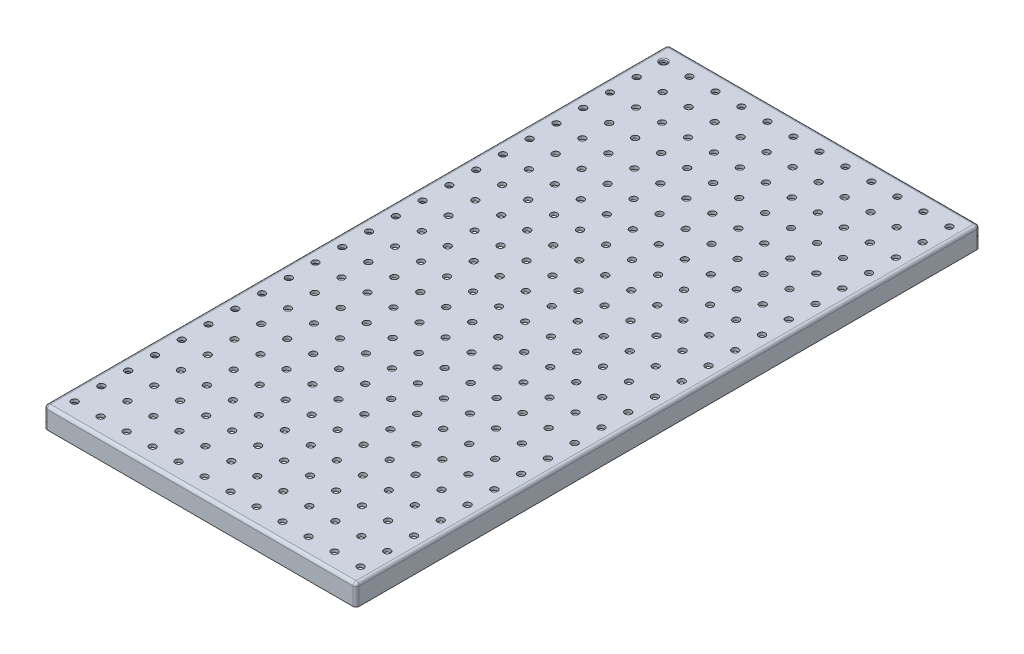
SolidWorks part; units mm, degrees
ref_plane "Alzado" through (0, 0, 0) normal (0, 0, 1) x (1, 0, 0)
ref_plane "Planta" through (0, 0, 0) normal (0, 1, 0) x (1, 0, 0)
ref_plane "Vista lateral" through (0, 0, 0) normal (1, 0, 0) x (0, 0, -1)
sketch "Croquis1" plane through (0, 0, 0) normal (0, 1, 0) x (1, 0, 0)
  line L1 (150, -300) -> (-150, -300)
  line L2 (150, -300) -> (150, 300)
  line L3 (150, 300) -> (-150, 300)
  line L4 (-150, -300) -> (-150, 300)
  line L5 (150, -300) -> (-150, 300) construction
  line L6 (150, 300) -> (-150, -300) construction
  point P0 (0, 0)
  dimension "D1" = 600
  dimension "D2" = 300
extrude "Saliente-Extruir1" add sketch "Croquis1" along normal blind 20
shell "Vaciado1" thickness 3 removed face at (0, 0, 0)
sketch "Croquis4" plane through (0, 20, 0) normal (0, 1, 0) x (1, 0, 0)
  line L0 (-137.5, 283.1945) -> (-137.5, 300) construction
  line L1 (150, 300) -> (-150, 300) construction
  line L2 (-137.5, 283.1945) -> (-150, 283.1945) construction
  line L3 (-150, 300) -> (-150, -300) construction
  line L4 (137.5, 283.1945) -> (150, 283.1945) construction
  line L5 (150, -300) -> (150, 300) construction
  line L6 (-137.5, 283.1945) -> (-112.5, 283.1945) construction
  line L7 (-137.5, 257.4495) -> (-125, 257.4495) construction
  line L8 (-125, 257.4495) -> (-125, 283.1945) construction
  line L9 (-112.5, -283.1945) -> (-112.5, -300) construction
  line L10 (-150, -300) -> (150, -300) construction
  circle A0 centre (-137.5, 283.1945) radius 3.175
  circle A1 centre (-112.5, 283.1945) radius 3.175
  circle A2 centre (-87.5, 283.1945) radius 3.175
  circle A3 centre (-62.5, 283.1945) radius 3.175
  circle A4 centre (-37.5, 283.1945) radius 3.175
  circle A5 centre (-12.5, 283.1945) radius 3.175
  circle A6 centre (12.5, 283.1945) radius 3.175
  circle A7 centre (37.5, 283.1945) radius 3.175
  circle A8 centre (62.5, 283.1945) radius 3.175
  circle A9 centre (87.5, 283.1945) radius 3.175
  circle A10 centre (112.5, 283.1945) radius 3.175
  circle A11 centre (137.5, 283.1945) radius 3.175
  circle A12 centre (-137.5, 257.4495) radius 3.175
  circle A13 centre (-112.5, 257.4495) radius 3.175
  circle A14 centre (-87.5, 257.4495) radius 3.175
  circle A15 centre (-62.5, 257.4495) radius 3.175
  circle A16 centre (-37.5, 257.4495) radius 3.175
  circle A17 centre (-12.5, 257.4495) radius 3.175
  circle A18 centre (12.5, 257.4495) radius 3.175
  circle A19 centre (37.5, 257.4495) radius 3.175
  circle A20 centre (62.5, 257.4495) radius 3.175
  circle A21 centre (87.5, 257.4495) radius 3.175
  circle A22 centre (112.5, 257.4495) radius 3.175
  circle A23 centre (137.5, 257.4495) radius 3.175
  circle A24 centre (-137.5, 231.7046) radius 3.175
  circle A25 centre (-112.5, 231.7046) radius 3.175
  circle A26 centre (-87.5, 231.7046) radius 3.175
  circle A27 centre (-62.5, 231.7046) radius 3.175
  circle A28 centre (-37.5, 231.7046) radius 3.175
  circle A29 centre (-12.5, 231.7046) radius 3.175
  circle A30 centre (12.5, 231.7046) radius 3.175
  circle A31 centre (37.5, 231.7046) radius 3.175
  circle A32 centre (62.5, 231.7046) radius 3.175
  circle A33 centre (87.5, 231.7046) radius 3.175
  circle A34 centre (112.5, 231.7046) radius 3.175
  circle A35 centre (137.5, 231.7046) radius 3.175
  circle A36 centre (-137.5, 205.9596) radius 3.175
  circle A37 centre (-112.5, 205.9596) radius 3.175
  circle A38 centre (-87.5, 205.9596) radius 3.175
  circle A39 centre (-62.5, 205.9596) radius 3.175
  circle A40 centre (-37.5, 205.9596) radius 3.175
  circle A41 centre (-12.5, 205.9596) radius 3.175
  circle A42 centre (12.5, 205.9596) radius 3.175
  circle A43 centre (37.5, 205.9596) radius 3.175
  circle A44 centre (62.5, 205.9596) radius 3.175
  circle A45 centre (87.5, 205.9596) radius 3.175
  circle A46 centre (112.5, 205.9596) radius 3.175
  circle A47 centre (137.5, 205.9596) radius 3.175
  circle A48 centre (-137.5, 180.2147) radius 3.175
  circle A49 centre (-112.5, 180.2147) radius 3.175
  circle A50 centre (-87.5, 180.2147) radius 3.175
  circle A51 centre (-62.5, 180.2147) radius 3.175
  circle A52 centre (-37.5, 180.2147) radius 3.175
  circle A53 centre (-12.5, 180.2147) radius 3.175
  circle A54 centre (12.5, 180.2147) radius 3.175
  circle A55 centre (37.5, 180.2147) radius 3.175
  circle A56 centre (62.5, 180.2147) radius 3.175
  circle A57 centre (87.5, 180.2147) radius 3.175
  circle A58 centre (112.5, 180.2147) radius 3.175
  circle A59 centre (137.5, 180.2147) radius 3.175
  circle A60 centre (-137.5, 154.4697) radius 3.175
  circle A61 centre (-112.5, 154.4697) radius 3.175
  circle A62 centre (-87.5, 154.4697) radius 3.175
  circle A63 centre (-62.5, 154.4697) radius 3.175
  circle A64 centre (-37.5, 154.4697) radius 3.175
  circle A65 centre (-12.5, 154.4697) radius 3.175
  circle A66 centre (12.5, 154.4697) radius 3.175
  circle A67 centre (37.5, 154.4697) radius 3.175
  circle A68 centre (62.5, 154.4697) radius 3.175
  circle A69 centre (87.5, 154.4697) radius 3.175
  circle A70 centre (112.5, 154.4697) radius 3.175
  circle A71 centre (137.5, 154.4697) radius 3.175
  circle A72 centre (-137.5, 128.7248) radius 3.175
  circle A73 centre (-112.5, 128.7248) radius 3.175
  circle A74 centre (-87.5, 128.7248) radius 3.175
  circle A75 centre (-62.5, 128.7248) radius 3.175
  circle A76 centre (-37.5, 128.7248) radius 3.175
  circle A77 centre (-12.5, 128.7248) radius 3.175
  circle A78 centre (12.5, 128.7248) radius 3.175
  circle A79 centre (37.5, 128.7248) radius 3.175
  circle A80 centre (62.5, 128.7248) radius 3.175
  circle A81 centre (87.5, 128.7248) radius 3.175
  circle A82 centre (112.5, 128.7248) radius 3.175
  circle A83 centre (137.5, 128.7248) radius 3.175
  circle A84 centre (-137.5, 102.9798) radius 3.175
  circle A85 centre (-112.5, 102.9798) radius 3.175
  circle A86 centre (-87.5, 102.9798) radius 3.175
  circle A87 centre (-62.5, 102.9798) radius 3.175
  circle A88 centre (-37.5, 102.9798) radius 3.175
  circle A89 centre (-12.5, 102.9798) radius 3.175
  circle A90 centre (12.5, 102.9798) radius 3.175
  circle A91 centre (37.5, 102.9798) radius 3.175
  circle A92 centre (62.5, 102.9798) radius 3.175
  circle A93 centre (87.5, 102.9798) radius 3.175
  circle A94 centre (112.5, 102.9798) radius 3.175
  circle A95 centre (137.5, 102.9798) radius 3.175
  circle A96 centre (-137.5, 77.2349) radius 3.175
  circle A97 centre (-112.5, 77.2349) radius 3.175
  circle A98 centre (-87.5, 77.2349) radius 3.175
  circle A99 centre (-62.5, 77.2349) radius 3.175
  circle A100 centre (-37.5, 77.2349) radius 3.175
  circle A101 centre (-12.5, 77.2349) radius 3.175
  circle A102 centre (12.5, 77.2349) radius 3.175
  circle A103 centre (37.5, 77.2349) radius 3.175
  circle A104 centre (62.5, 77.2349) radius 3.175
  circle A105 centre (87.5, 77.2349) radius 3.175
  circle A106 centre (112.5, 77.2349) radius 3.175
  circle A107 centre (137.5, 77.2349) radius 3.175
  circle A108 centre (-137.5, 51.4899) radius 3.175
  circle A109 centre (-112.5, 51.4899) radius 3.175
  circle A110 centre (-87.5, 51.4899) radius 3.175
  circle A111 centre (-62.5, 51.4899) radius 3.175
  circle A112 centre (-37.5, 51.4899) radius 3.175
  circle A113 centre (-12.5, 51.4899) radius 3.175
  circle A114 centre (12.5, 51.4899) radius 3.175
  circle A115 centre (37.5, 51.4899) radius 3.175
  circle A116 centre (62.5, 51.4899) radius 3.175
  circle A117 centre (87.5, 51.4899) radius 3.175
  circle A118 centre (112.5, 51.4899) radius 3.175
  circle A119 centre (137.5, 51.4899) radius 3.175
  circle A120 centre (-137.5, 25.745) radius 3.175
  circle A121 centre (-112.5, 25.745) radius 3.175
  circle A122 centre (-87.5, 25.745) radius 3.175
  circle A123 centre (-62.5, 25.745) radius 3.175
  circle A124 centre (-37.5, 25.745) radius 3.175
  circle A125 centre (-12.5, 25.745) radius 3.175
  circle A126 centre (12.5, 25.745) radius 3.175
  circle A127 centre (37.5, 25.745) radius 3.175
  circle A128 centre (62.5, 25.745) radius 3.175
  circle A129 centre (87.5, 25.745) radius 3.175
  circle A130 centre (112.5, 25.745) radius 3.175
  circle A131 centre (137.5, 25.745) radius 3.175
  circle A132 centre (-137.5, 0) radius 3.175
  circle A133 centre (-112.5, 0) radius 3.175
  circle A134 centre (-87.5, 0) radius 3.175
  circle A135 centre (-62.5, 0) radius 3.175
  circle A136 centre (-37.5, 0) radius 3.175
  circle A137 centre (-12.5, 0) radius 3.175
  circle A138 centre (12.5, 0) radius 3.175
  circle A139 centre (37.5, 0) radius 3.175
  circle A140 centre (62.5, 0) radius 3.175
  circle A141 centre (87.5, 0) radius 3.175
  circle A142 centre (112.5, 0) radius 3.175
  circle A143 centre (137.5, 0) radius 3.175
  circle A144 centre (-137.5, -25.745) radius 3.175
  circle A145 centre (-112.5, -25.745) radius 3.175
  circle A146 centre (-87.5, -25.745) radius 3.175
  circle A147 centre (-62.5, -25.745) radius 3.175
  circle A148 centre (-37.5, -25.745) radius 3.175
  circle A149 centre (-12.5, -25.745) radius 3.175
  circle A150 centre (12.5, -25.745) radius 3.175
  circle A151 centre (37.5, -25.745) radius 3.175
  circle A152 centre (62.5, -25.745) radius 3.175
  circle A153 centre (87.5, -25.745) radius 3.175
  circle A154 centre (112.5, -25.745) radius 3.175
  circle A155 centre (137.5, -25.745) radius 3.175
  circle A156 centre (-137.5, -51.4899) radius 3.175
  circle A157 centre (-112.5, -51.4899) radius 3.175
  circle A158 centre (-87.5, -51.4899) radius 3.175
  circle A159 centre (-62.5, -51.4899) radius 3.175
  circle A160 centre (-37.5, -51.4899) radius 3.175
  circle A161 centre (-12.5, -51.4899) radius 3.175
  circle A162 centre (12.5, -51.4899) radius 3.175
  circle A163 centre (37.5, -51.4899) radius 3.175
  circle A164 centre (62.5, -51.4899) radius 3.175
  circle A165 centre (87.5, -51.4899) radius 3.175
  circle A166 centre (112.5, -51.4899) radius 3.175
  circle A167 centre (137.5, -51.4899) radius 3.175
  circle A168 centre (-137.5, -77.2349) radius 3.175
  circle A169 centre (-112.5, -77.2349) radius 3.175
  circle A170 centre (-87.5, -77.2349) radius 3.175
  circle A171 centre (-62.5, -77.2349) radius 3.175
  circle A172 centre (-37.5, -77.2349) radius 3.175
  circle A173 centre (-12.5, -77.2349) radius 3.175
  circle A174 centre (12.5, -77.2349) radius 3.175
  circle A175 centre (37.5, -77.2349) radius 3.175
  circle A176 centre (62.5, -77.2349) radius 3.175
  circle A177 centre (87.5, -77.2349) radius 3.175
  circle A178 centre (112.5, -77.2349) radius 3.175
  circle A179 centre (137.5, -77.2349) radius 3.175
  circle A180 centre (-137.5, -102.9798) radius 3.175
  circle A181 centre (-112.5, -102.9798) radius 3.175
  circle A182 centre (-87.5, -102.9798) radius 3.175
  circle A183 centre (-62.5, -102.9798) radius 3.175
  circle A184 centre (-37.5, -102.9798) radius 3.175
  circle A185 centre (-12.5, -102.9798) radius 3.175
  circle A186 centre (12.5, -102.9798) radius 3.175
  circle A187 centre (37.5, -102.9798) radius 3.175
  circle A188 centre (62.5, -102.9798) radius 3.175
  circle A189 centre (87.5, -102.9798) radius 3.175
  circle A190 centre (112.5, -102.9798) radius 3.175
  circle A191 centre (137.5, -102.9798) radius 3.175
  circle A192 centre (-137.5, -128.7248) radius 3.175
  circle A193 centre (-112.5, -128.7248) radius 3.175
  circle A194 centre (-87.5, -128.7248) radius 3.175
  circle A195 centre (-62.5, -128.7248) radius 3.175
  circle A196 centre (-37.5, -128.7248) radius 3.175
  circle A197 centre (-12.5, -128.7248) radius 3.175
  circle A198 centre (12.5, -128.7248) radius 3.175
  circle A199 centre (37.5, -128.7248) radius 3.175
  circle A200 centre (62.5, -128.7248) radius 3.175
  circle A201 centre (87.5, -128.7248) radius 3.175
  circle A202 centre (112.5, -128.7248) radius 3.175
  circle A203 centre (137.5, -128.7248) radius 3.175
  circle A204 centre (-137.5, -154.4697) radius 3.175
  circle A205 centre (-112.5, -154.4697) radius 3.175
  circle A206 centre (-87.5, -154.4697) radius 3.175
  circle A207 centre (-62.5, -154.4697) radius 3.175
  circle A208 centre (-37.5, -154.4697) radius 3.175
  circle A209 centre (-12.5, -154.4697) radius 3.175
  circle A210 centre (12.5, -154.4697) radius 3.175
  circle A211 centre (37.5, -154.4697) radius 3.175
  circle A212 centre (62.5, -154.4697) radius 3.175
  circle A213 centre (87.5, -154.4697) radius 3.175
  circle A214 centre (112.5, -154.4697) radius 3.175
  circle A215 centre (137.5, -154.4697) radius 3.175
  circle A216 centre (-137.5, -180.2147) radius 3.175
  circle A217 centre (-112.5, -180.2147) radius 3.175
  circle A218 centre (-87.5, -180.2147) radius 3.175
  circle A219 centre (-62.5, -180.2147) radius 3.175
  circle A220 centre (-37.5, -180.2147) radius 3.175
  circle A221 centre (-12.5, -180.2147) radius 3.175
  circle A222 centre (12.5, -180.2147) radius 3.175
  circle A223 centre (37.5, -180.2147) radius 3.175
  circle A224 centre (62.5, -180.2147) radius 3.175
  circle A225 centre (87.5, -180.2147) radius 3.175
  circle A226 centre (112.5, -180.2147) radius 3.175
  circle A227 centre (137.5, -180.2147) radius 3.175
  circle A228 centre (-137.5, -205.9596) radius 3.175
  circle A229 centre (-112.5, -205.9596) radius 3.175
  circle A230 centre (-87.5, -205.9596) radius 3.175
  circle A231 centre (-62.5, -205.9596) radius 3.175
  circle A232 centre (-37.5, -205.9596) radius 3.175
  circle A233 centre (-12.5, -205.9596) radius 3.175
  circle A234 centre (12.5, -205.9596) radius 3.175
  circle A235 centre (37.5, -205.9596) radius 3.175
  circle A236 centre (62.5, -205.9596) radius 3.175
  circle A237 centre (87.5, -205.9596) radius 3.175
  circle A238 centre (112.5, -205.9596) radius 3.175
  circle A239 centre (137.5, -205.9596) radius 3.175
  circle A240 centre (-137.5, -231.7046) radius 3.175
  circle A241 centre (-112.5, -231.7046) radius 3.175
  circle A242 centre (-87.5, -231.7046) radius 3.175
  circle A243 centre (-62.5, -231.7046) radius 3.175
  circle A244 centre (-37.5, -231.7046) radius 3.175
  circle A245 centre (-12.5, -231.7046) radius 3.175
  circle A246 centre (12.5, -231.7046) radius 3.175
  circle A247 centre (37.5, -231.7046) radius 3.175
  circle A248 centre (62.5, -231.7046) radius 3.175
  circle A249 centre (87.5, -231.7046) radius 3.175
  circle A250 centre (112.5, -231.7046) radius 3.175
  circle A251 centre (137.5, -231.7046) radius 3.175
  circle A252 centre (-137.5, -257.4495) radius 3.175
  circle A253 centre (-112.5, -257.4495) radius 3.175
  circle A254 centre (-87.5, -257.4495) radius 3.175
  circle A255 centre (-62.5, -257.4495) radius 3.175
  circle A256 centre (-37.5, -257.4495) radius 3.175
  circle A257 centre (-12.5, -257.4495) radius 3.175
  circle A258 centre (12.5, -257.4495) radius 3.175
  circle A259 centre (37.5, -257.4495) radius 3.175
  circle A260 centre (62.5, -257.4495) radius 3.175
  circle A261 centre (87.5, -257.4495) radius 3.175
  circle A262 centre (112.5, -257.4495) radius 3.175
  circle A263 centre (137.5, -257.4495) radius 3.175
  circle A264 centre (-137.5, -283.1945) radius 3.175
  circle A265 centre (-112.5, -283.1945) radius 3.175
  circle A266 centre (-87.5, -283.1945) radius 3.175
  circle A267 centre (-62.5, -283.1945) radius 3.175
  circle A268 centre (-37.5, -283.1945) radius 3.175
  circle A269 centre (-12.5, -283.1945) radius 3.175
  circle A270 centre (12.5, -283.1945) radius 3.175
  circle A271 centre (37.5, -283.1945) radius 3.175
  circle A272 centre (62.5, -283.1945) radius 3.175
  circle A273 centre (87.5, -283.1945) radius 3.175
  circle A274 centre (112.5, -283.1945) radius 3.175
  circle A275 centre (137.5, -283.1945) radius 3.175
  point P444 (-125, 283.1945)
  dimension "D1" = 6.35
  dimension "D2" = 12
  dimension "D3" = 23
extrude "Cortar-Extruir1" cut sketch "Croquis4" against normal blind 10
fillet "Redondeo1" radius 3 4 edges at (150, 10, 300) (-150, 10, 300) (150, 10, -300) (-150, 10, -300)
fillet "Redondeo2" radius 3 8 edges at (149.1213, 20, -299.1213) (150, 20, 0) (149.1213, 20, 299.1213) (0, 20, 300) (-149.1213, 20, 299.1213) (-150, 20, 0) (-149.1213, 20, -299.1213) (0, 20, -300)
fillet "Redondeo3" radius 1 1 edges at (-137.5, 20, -280.0195)
